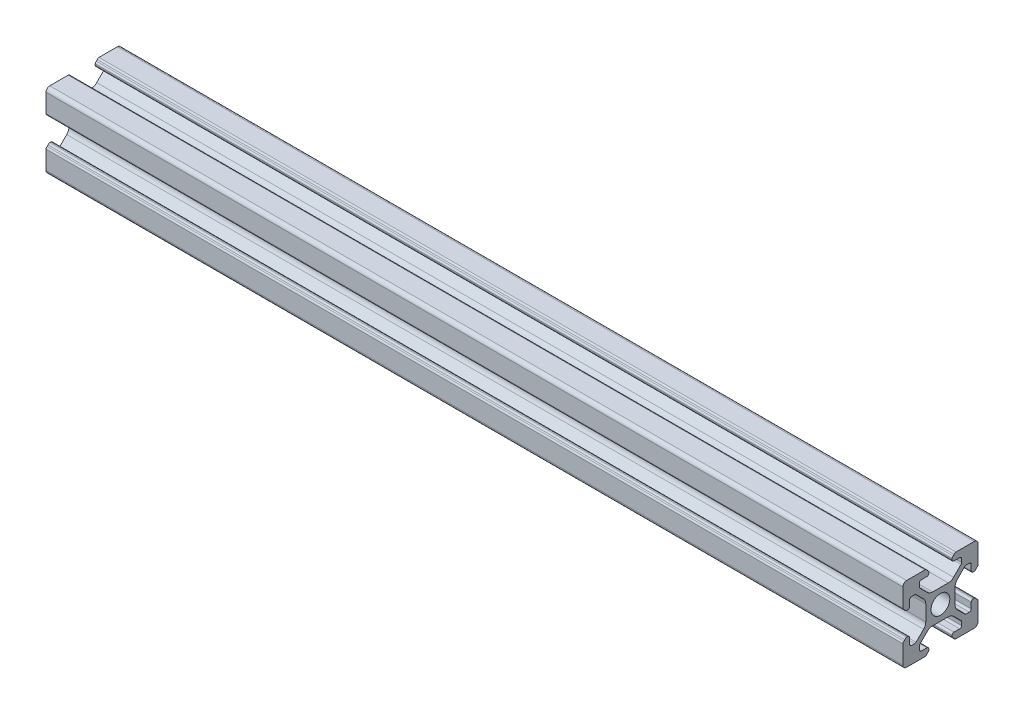
SolidWorks part; units mm, degrees
material "6063-O, Extruded Rod (SS)"
ref_plane "Front Plane" through (0, 0, 0) normal (0, 0, 1) x (1, 0, 0)
ref_plane "Top Plane" through (0, 0, 0) normal (0, 1, 0) x (1, 0, 0)
ref_plane "Right Plane" through (0, 0, 0) normal (1, 0, 0) x (0, 0, -1)
sketch "Sketch1" plane through (0, 0, 0) normal (1, 0, 0) x (0, 0, -1)
  line L0 (10, 10) -> (-10, -10) construction
  line L1 (-10, 10) -> (10, 10)
  line L2 (-10, 10) -> (-10, -10)
  line L3 (-10, -10) -> (10, -10)
  line L4 (10, 10) -> (10, -10)
  dimension "D1" = 20
extrude "Boss-Extrude1" add sketch "Sketch1" along normal blind 228
fillet "Fillet1" radius 1 4 edges at (114, -10, -10) (114, -10, 10) (114, 10, -10) (114, 10, 10)
sketch "Sketch3" plane through (0, 0, 0) normal (-1, 0, 0) x (0, 0, 1)
  line L0 (-3.6, 10) -> (3.6, 10)
  line L1 (-9, 10) -> (9, 10) construction
  line L2 (3.6, 10) -> (3.6, 9.5)
  line L3 (3.6, 9.5) -> (3.1, 9.5)
  line L4 (3.1, 9.5) -> (3.1, 8.2)
  line L5 (3.1, 8.2) -> (5.63, 8.2)
  line L6 (5.63, 8.2) -> (5.63, 6.6199)
  line L7 (5.63, 6.6199) -> (2.9101, 3.9)
  line L8 (2.9101, 3.9) -> (-2.9101, 3.9)
  line L9 (-2.9101, 3.9) -> (-5.63, 6.6199)
  line L10 (-5.63, 6.6199) -> (-5.63, 8.2)
  line L11 (-5.63, 8.2) -> (-3.1, 8.2)
  line L12 (-3.1, 8.2) -> (-3.1, 9.5)
  line L13 (-3.1, 9.5) -> (-3.6, 9.5)
  line L14 (-3.6, 9.5) -> (-3.6, 10)
  line L15 (0, 10) -> (0, 3.9) construction
  line L16 (10, 3.6) -> (10, -3.6)
  line L17 (10, -3.6) -> (9.5, -3.6)
  line L18 (9.5, -3.6) -> (9.5, -3.1)
  line L19 (9.5, -3.1) -> (8.2, -3.1)
  line L20 (8.2, -3.1) -> (8.2, -5.63)
  line L21 (8.2, -5.63) -> (6.6199, -5.63)
  line L22 (6.6199, -5.63) -> (3.9, -2.9101)
  line L23 (3.9, -2.9101) -> (3.9, 2.9101)
  line L24 (3.9, 2.9101) -> (6.6199, 5.63)
  line L25 (6.6199, 5.63) -> (8.2, 5.63)
  line L26 (8.2, 5.63) -> (8.2, 3.1)
  line L27 (8.2, 3.1) -> (9.5, 3.1)
  line L28 (9.5, 3.1) -> (9.5, 3.6)
  line L29 (9.5, 3.6) -> (10, 3.6)
  line L30 (10, 0) -> (3.9, 0) construction
  line L31 (3.6, -10) -> (-3.6, -10)
  line L32 (-3.6, -10) -> (-3.6, -9.5)
  line L33 (-3.6, -9.5) -> (-3.1, -9.5)
  line L34 (-3.1, -9.5) -> (-3.1, -8.2)
  line L35 (-3.1, -8.2) -> (-5.63, -8.2)
  line L36 (-5.63, -8.2) -> (-5.63, -6.6199)
  line L37 (-5.63, -6.6199) -> (-2.9101, -3.9)
  line L38 (-2.9101, -3.9) -> (2.9101, -3.9)
  line L39 (2.9101, -3.9) -> (5.63, -6.6199)
  line L40 (5.63, -6.6199) -> (5.63, -8.2)
  line L41 (5.63, -8.2) -> (3.1, -8.2)
  line L42 (3.1, -8.2) -> (3.1, -9.5)
  line L43 (3.1, -9.5) -> (3.6, -9.5)
  line L44 (3.6, -9.5) -> (3.6, -10)
  line L45 (0, -10) -> (0, -3.9) construction
  line L46 (-10, -3.6) -> (-10, 3.6)
  line L47 (-10, 3.6) -> (-9.5, 3.6)
  line L48 (-9.5, 3.6) -> (-9.5, 3.1)
  line L49 (-9.5, 3.1) -> (-8.2, 3.1)
  line L50 (-8.2, 3.1) -> (-8.2, 5.63)
  line L51 (-8.2, 5.63) -> (-6.6199, 5.63)
  line L52 (-6.6199, 5.63) -> (-3.9, 2.9101)
  line L53 (-3.9, 2.9101) -> (-3.9, -2.9101)
  line L54 (-3.9, -2.9101) -> (-6.6199, -5.63)
  line L55 (-6.6199, -5.63) -> (-8.2, -5.63)
  line L56 (-8.2, -5.63) -> (-8.2, -3.1)
  line L57 (-8.2, -3.1) -> (-9.5, -3.1)
  line L58 (-9.5, -3.1) -> (-9.5, -3.6)
  line L59 (-9.5, -3.6) -> (-10, -3.6)
  line L60 (-10, 0) -> (-3.9, 0) construction
  line L61 (10, 9) -> (10, -9) construction
  line L62 (-10, -9) -> (-10, 9) construction
  point P4 (0, 10)
  point P17 (0, 0)
  point P26 (10, 0)
  point P43 (0, -10)
  point P60 (-10, 0)
  point P75 (0, 0)
  dimension "D1" = 135
  dimension "D2" = 6.2
  dimension "D3" = 7.2
  dimension "D4" = 6.1
  dimension "D5" = 11.26
  dimension "D6" = 0.5
  dimension "D8" = 1.4
  dimension "D9" = 1.8
  dimension "D7" = 4
extrude "Cut-Extrude1" cut sketch "Sketch3" against normal through all
hole_wizard "Ø5.0 (5) Diameter Hole1" positions "Sketch4" profile "Sketch5" hole size "Ø5.0" standard "ANSI Metric" end condition through all
sketch "Sketch4" plane through (0, 0, 0) normal (-1, 0, 0) x (0, 0, 1)
  point P0 (0, 0)
sketch "Sketch5" plane through (0, 0, 0) normal (0, 1, 0) x (0, 0, 1)
  line L0 (0, 0) -> (0, 228)
  line L1 (0, 228) -> (2.5, 228)
  line L2 (2.5, 228) -> (2.5, 0)
  line L5 (2.5, 0) -> (0, 0)
  line L11 (0, -6.35) -> (0, 107.95) construction
  dimension "Thru Hole Dia." = 5
  dimension "Thru Hole Depth" = 228
fillet "Fillet2" radius 2 8 edges at (114, -3.9, -2.9101) (114, -3.9, 2.9101) (114, -2.9101, 3.9) (114, 2.9101, 3.9) (114, 3.9, 2.9101) (114, 3.9, -2.9101) (114, 2.9101, -3.9) (114, -2.9101, -3.9)
fillet "Fillet3" radius 0.5 20 edges at (114, 3.6, -10) (114, 3.1, -9.5) (114, 3.1, -8.2) (114, 5.63, -8.2) (114, 5.63, -6.6199) (114, 3.6, 10) (114, 3.1, 9.5) (114, 3.1, 8.2) (114, 5.63, 8.2) (114, 5.63, 6.6199) (114, 6.6199, 5.63) (114, 8.2, 5.63) (114, 8.2, 3.1) (114, 9.5, 3.1) (114, 10, 3.6) (114, 9.5, -3.1) (114, 10, -3.6) (114, 8.2, -3.1) (114, 8.2, -5.63) (114, 6.6199, -5.63)
fillet "Fillet4" radius 0.5 20 edges at (114, -3.6, 10) (114, -3.1, 9.5) (114, -3.1, 8.2) (114, -5.63, 8.2) (114, -5.63, 6.6199) (114, -6.6199, 5.63) (114, -8.2, 5.63) (114, -8.2, 3.1) (114, -10, 3.6) (114, -9.5, 3.1) (114, -10, -3.6) (114, -9.5, -3.1) (114, -8.2, -3.1) (114, -8.2, -5.63) (114, -6.6199, -5.63) (114, -5.63, -6.6199) (114, -5.63, -8.2) (114, -3.1, -8.2) (114, -3.1, -9.5) (114, -3.6, -10)
fillet "Fillet5" radius 0.5 8 edges at (114, 3.6, -9.5) (114, -3.6, -9.5) (114, -9.5, -3.6) (114, -9.5, 3.6) (114, -3.6, 9.5) (114, 3.6, 9.5) (114, 9.5, 3.6) (114, 9.5, -3.6)
